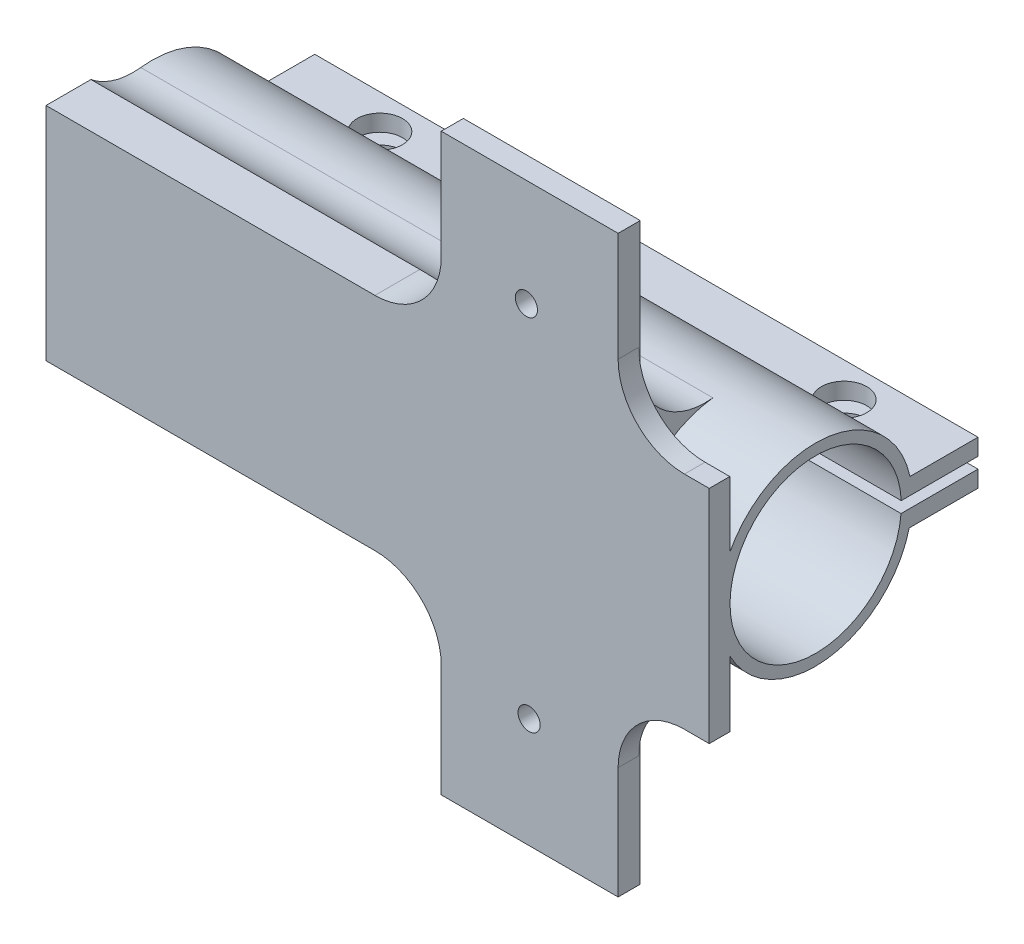
SolidWorks part; units mm, degrees
ref_plane "Front Plane" through (0, 0, 0) normal (0, 0, 1) x (1, 0, 0)
ref_plane "Top Plane" through (0, 0, 0) normal (0, 1, 0) x (1, 0, 0)
ref_plane "Right Plane" through (0, 0, 0) normal (1, 0, 0) x (0, 0, -1)
sketch "Sketch1" plane through (0, 0, 0) normal (1, 0, 0) x (0, 0, -1)
  line L1 (0, 0) -> (0.93, 0)
  line L2 (0, 0) -> (0, 10)
  line L3 (0, 10) -> (0.93, 10)
  line L4 (0.93, 0) -> (0.93, 10)
  circle A0 centre (4.805, 5) radius 3.875
  circle A1 centre (4.805, 5) radius 4.375
  dimension "D1" = 7.75
  dimension "D4" = 8.75
  dimension "D2" = 10
  dimension "D3" = 5
extrude "Boss-Extrude1" add sketch "Sketch1" along normal blind 30 contours A1 | L2 L1 L4 L3
sketch "Sketch2" plane through (0, 0, 0) normal (0, 0, 1) x (1, 0, 0)
  line L1 (25.8783, -8.0689) -> (17.8783, -8.0689)
  line L2 (25.8783, -8.0689) -> (25.8783, 17.9311)
  line L3 (25.8783, 17.9311) -> (17.8783, 17.9311)
  line L4 (17.8783, -8.0689) -> (17.8783, 17.9311)
  line L5 (25.8783, -8.0689) -> (17.8783, 17.9311) construction
  line L6 (25.8783, 17.9311) -> (17.8783, -8.0689) construction
  point P0 (21.8783, 4.9311)
  dimension "D1" = 26
  dimension "D2" = 8
extrude "Boss-Extrude3" add sketch "Sketch2" against normal blind 1
fillet "Fillet4" radius 3 4 edges at (25.8783, 10, -0.465) (17.8783, 10, -0.465) (17.8783, 0, -0.465) (25.8783, 0, -0.465)
fillet "Fillet5" radius 3 2 edges at (8.9391, 7.031, -0.93) (8.9391, 2.969, -0.93)
sketch "Sketch3" plane through (0, 0, -1) normal (0, 0, -1) x (-1, 0, 0)
  line L0 (-25.8783, 11.6786) -> (-17.8783, 11.6786) construction
  circle A0 centre (-21.7302, 13.0986) radius 0.5
  circle A1 centre (-21.8517, -3.1009) radius 0.5
  point P4 (0, 0)
  point P7 (0, 0)
  point P10 (0, 0)
  dimension "D2" = 1
  dimension "D3" = 1
  dimension "D4" = 1.42
  dimension "D1" = 16.2
extrude "Cut-Extrude1" cut sketch "Sketch3" against normal up to next
sketch "Sketch4" plane through (30, 0, 0) normal (1, 0, 0) x (0, 0, -1)
  line L1 (2.1571, 5.9265) -> (12.1571, 5.9265)
  line L2 (2.1571, 5.9265) -> (2.1571, 3.9265)
  line L3 (2.1571, 3.9265) -> (12.1571, 3.9265)
  line L4 (12.1571, 5.9265) -> (12.1571, 3.9265)
  dimension "D2" = 2
  dimension "D1" = 10
extrude "Boss-Extrude4" add sketch "Sketch4" against normal blind 30
sketch "Sketch5" plane through (30, 0, 0) normal (1, 0, 0) x (0, 0, -1)
  circle A0 centre (4.8153, 5) radius 3.875
  dimension "D1" = 7.75
extrude "Cut-Extrude2" cut sketch "Sketch5" against normal up to next
sketch "Sketch6" plane through (30, 0, 0) normal (1, 0, 0) x (0, 0, -1)
  line L0 (12.1571, 5.1765) -> (12.1571, 4.6765)
  line L1 (12.1571, 3.9265) -> (12.1571, 5.9265) construction
  line L2 (12.1571, 4.6765) -> (8.6768, 4.6765)
  line L3 (8.6863, 5.1765) -> (12.1571, 5.1765)
  line L4 (12.1571, 5.9265) -> (9.0808, 5.9265) construction
  line L5 (9.0463, 3.9265) -> (12.1571, 3.9265) construction
  circle A0 centre (4.8153, 5) radius 3.875 construction
  spline S0 degree 2 poles (8.6768, 4.6765) (8.6977, 4.9264) (8.6863, 5.1765) knots 0 0 0 1 1 1
  dimension "D1" = 0.75
  dimension "D2" = 0.75
extrude "Cut-Extrude4" cut sketch "Sketch6" against normal up to next
hole_wizard "M2.5x0.45 Tapped Hole1" positions "Sketch7" profile "Sketch8" tap size "M2.5x0.45" standard "ANSI Metric" end condition through all
sketch "Sketch7" plane through (0, 3.9265, 0) normal (0, -1, 0) x (-1, 0, 0)
  line L0 (-30, 9.0463) -> (-30, 12.1571) construction
  line L1 (0, 9.0463) -> (0, 12.1571) construction
  point P0 (-25.5, 10.5993)
  point P2 (-4.5, 10.5993)
  dimension "D1" = 4.5
  dimension "D2" = 4.5
sketch "Sketch8" plane through (25.5, 3.9265, -10.5993) normal (1, 0, 0) x (0, 0, -1)
  line L0 (0, 0) -> (0, 14.0046)
  line L1 (0, 14.0046) -> (1.025, 14.0046)
  line L2 (1.025, 14.0046) -> (1.025, 0.25)
  line L3 (1.025, 0.25) -> (1.275, 0)
  line L5 (1.275, 0) -> (0, 0)
  line L6 (-1.025, 0.25) -> (-1.275, 0) construction
  line L11 (0, -6.35) -> (0, 107.95) construction
  dimension "Thru Tap Drill Dia." = 2.05
  dimension "Thru Tap Drill Depth" = 14.0046
  dimension "Near C'Sink Dia." = 2.55
  dimension "Near C'Sink Angle" = 90
cosmetic thread "Hole Thread1" parameters "D2"=2.5
cosmetic thread "Hole Thread2" parameters "D2"=2.5
